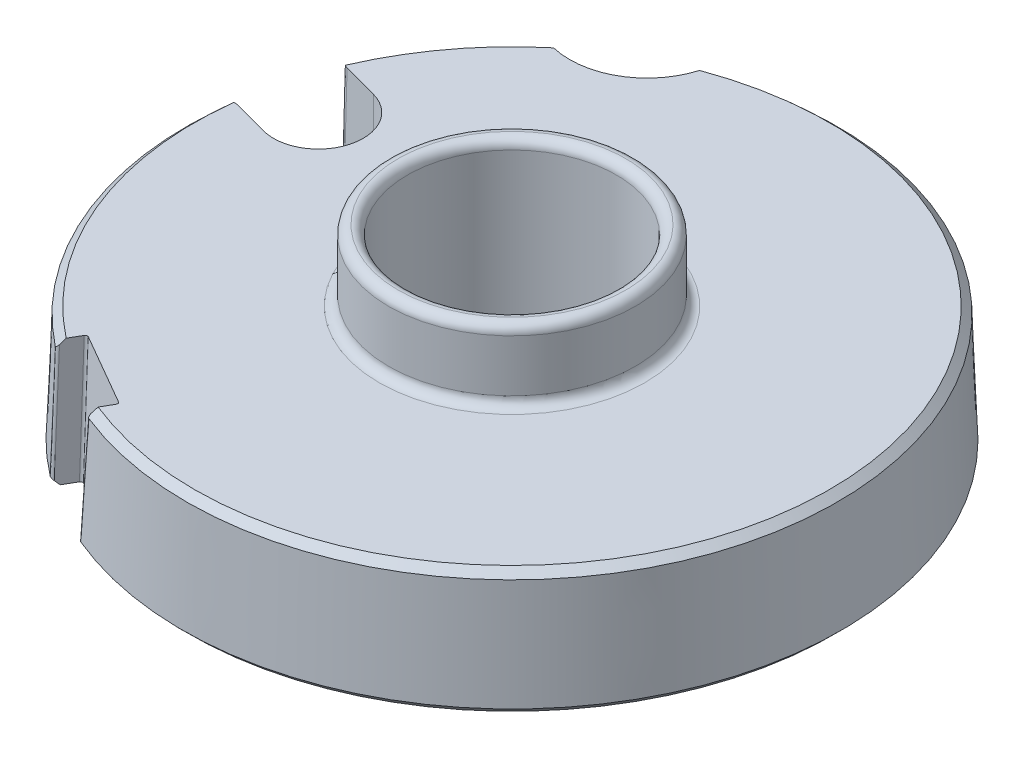
SolidWorks part; units mm, degrees
other "Markup1"
sketch "Sketch2" plane through (35, 13, 35) normal (0.2948, 0.542, 0.787) x (0.936, 0.0019, -0.3519)
sketch "Sketch9" plane through (35, 20.5, 35) normal (0.2948, 0.542, 0.787) x (0.936, 0.0019, -0.3519)
sketch "Sketch11" plane through (35, 20.5, 35) normal (0.2948, 0.542, 0.787) x (0.936, 0.0019, -0.3519)
other "Markup2"
sketch "Sketch4" plane through (-35, 13, -35) normal (-0.7629, 0.6068, -0.2233) x (-0.2746, 0.0085, 0.9615)
sketch "Sketch10" plane through (-35, 20.5, -35) normal (-0.7629, 0.6068, -0.2233) x (-0.2746, 0.0085, 0.9615)
sketch "Sketch12" plane through (-35, 20.5, -35) normal (-0.7629, 0.6068, -0.2233) x (-0.2746, 0.0085, 0.9615)
other "Markup3"
sketch "Sketch13" plane through (-34.8971, -0.0847, -34.8971) normal (0, -1, 0) x (1, 0, 0)
ref_plane "Front Plane" through (0, 0, 0) normal (0, 0, 1) x (1, 0, 0)
ref_plane "Top Plane" through (0, 0, 0) normal (0, 1, 0) x (1, 0, 0)
ref_plane "Right Plane" through (0, 0, 0) normal (1, 0, 0) x (0, 0, -1)
sketch "Sketch1" plane through (0, 0, 0) normal (0, 1, 0) x (1, 0, 0)
  circle A0 centre (0, 0) radius 34.925
  dimension "D1" = 69.85
extrude "Boss-Extrude1" add sketch "Sketch1" along normal blind 13 draft 2.21
chamfer "Chamfer1" distance 0.75 angle 45 2 edges at (0, 0, 34.925) (0, 13, 34.4233) first distance on face at (0, 0, 34.925) first distance on face at (0, 13, 34.4233)
sketch "Sketch3" plane through (0, 0, 0) normal (0, 1, 0) x (1, 0, 0)
  line L0 (0, 0) -> (-17.4625, 30.2459) construction
  line L1 (0, 0) -> (34.925, 0) construction
  line L2 (0, 0) -> (-17.4625, -30.2459) construction
  line L3 (-11.275, 0) -> (11.275, 0) construction
  circle A0 centre (0, 0) radius 34.925 construction
  arc A2 (-22.0077, 27.1185) -> (-12.4815, 32.6185) centre (0, 0) cw
  arc A4 (-22.0077, 27.1185) -> (-12.4815, 32.6185) centre (-19.5523, 33.8656) ccw
  point P12 (0, 0)
  dimension "D4" = 5.5
  dimension "D5" = 7.18
  dimension "D2" = 120
  dimension "D3" = 11
  dimension "D1" = 3
extrude "Cut-Extrude1" cut sketch "Sketch3" along normal blind 13 draft 4.5 draft outward yes
sketch "Sketch5" plane through (0, 0, 0) normal (0, 1, 0) x (1, 0, 0)
  line L0 (0, 0) -> (-17.4625, -30.2459) construction
  line L1 (-11.275, 0) -> (11.275, 0) construction
  line L2 (-12.5151, -29.9269) -> (-19.6599, -25.8019)
  line L3 (-12.5151, -29.9269) -> (-15.2651, -34.69)
  line L4 (-19.6599, -25.8019) -> (-22.4099, -30.565)
  line L5 (-15.2651, -34.69) -> (-22.4099, -30.565)
  line L6 (-12.5151, -29.9269) -> (-22.4099, -30.565) construction
  line L7 (-19.6599, -25.8019) -> (-15.2651, -34.69) construction
  arc A0 (-12.4815, 32.6185) -> (-22.0077, 27.1185) centre (0, 0) ccw construction
  dimension "D1" = 60
  dimension "D2" = 2.75
  dimension "D3" = 8.25
  dimension "D4" = 90
extrude "Cut-Extrude2" cut sketch "Sketch5" along normal blind 13 draft 2.2 draft outward yes
sketch "Sketch8" plane through (0, 0, 0) normal (0, -1, 0) x (1, 0, 0)
  line L0 (0, 0) -> (-28.0118, -7.5058) construction
  line L1 (0, -11.275) -> (0, 11.275) construction
  line L2 (-28.0118, -7.5058) -> (-35.7393, -9.5763) construction
  line L3 (-26.7825, -12.0939) -> (-34.5099, -14.1645)
  line L4 (-29.2412, -2.9176) -> (-36.9686, -4.9882)
  arc A2 (-26.7825, -12.0939) -> (-29.2412, -2.9176) centre (-28.0118, -7.5058) ccw
  arc A3 (-36.9686, -4.9882) -> (-34.5099, -14.1645) centre (-35.7393, -9.5763) ccw
  point P1 (-31.8756, -8.541)
  dimension "D1" = 4.75
  dimension "D2" = 29
  dimension "D3" = 75
  dimension "D4" = 8
extrude "Cut-Extrude4" cut sketch "Sketch8" against normal blind 17.5
fillet "Fillet1" radius 0.25 6 edges at (-12.174, 6.5, 29.8355) (-19.7513, 6.5, 25.4608)
sketch "Sketch6" plane through (0, 13, 0) normal (0, 1, 0) x (1, 0, 0)
  circle A0 centre (0, 0) radius 11.0625
  dimension "D1" = 22.125
extrude "Cut-Extrude3" cut sketch "Sketch6" against normal blind 13
sketch "Sketch7" plane through (0, 13, 0) normal (0, 1, 0) x (1, 0, 0)
  circle A0 centre (0, 0) radius 11.0625
  circle A1 centre (0, 0) radius 13.0625
  dimension "D1" = 22.125
  dimension "D2" = 26.125
extrude "Boss-Extrude2" add sketch "Sketch7" along normal blind 7.5
fillet "Fillet2" radius 1 5 edges at (0, 20.5, 11.0625) (0, 20.5, 13.0625) (0, 13, 13.0625)
